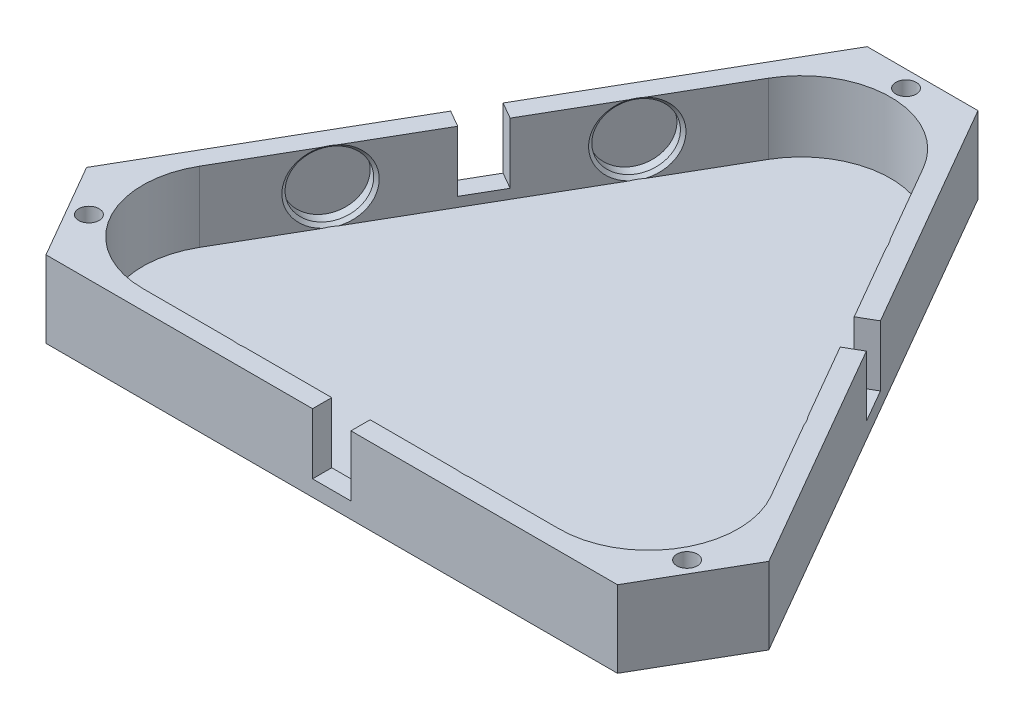
SolidWorks part; units mm, degrees
ref_plane "Plan de face" through (0, 0, 0) normal (0, 0, 1) x (1, 0, 0)
ref_plane "Plan de dessus" through (0, 0, 0) normal (0, 1, 0) x (1, 0, 0)
ref_plane "Plan de droite" through (0, 0, 0) normal (1, 0, 0) x (0, 0, -1)
sketch "Esquisse1" plane through (0, 0, 0) normal (0, 1, 0) x (1, 0, 0)
  line L3 (-62, -35.7957) -> (62, -35.7957)
  line L4 (62, -35.7957) -> (0, 71.5914)
  line L5 (0, 71.5914) -> (-62, -35.7957)
  line L6 (0, 71.5914) -> (0, -35.7957) construction
  line L7 (62, -35.7957) -> (-31, 17.8979) construction
  dimension "D1" = 124
extrude "Boss.-Extru.1" add sketch "Esquisse1" along normal blind 12 separate body
ref_axis "Axe1" through (0, -0.9, 0) along (0, 1, 0)
sketch "Esquisse10" plane through (0, 12, 0) normal (0, 1, 0) x (1, 0, 0)
  circle A0 centre (0, 54) radius 1.6
  circle A1 centre (46.7654, -27) radius 1.6
  circle A2 centre (-46.7654, -27) radius 1.6
  point P9 (0, 0)
  dimension "D1" = 3.2
  dimension "D2" = 54
  dimension "D3" = 3
extrude "Enlèv. mat.-Extru.6" cut sketch "Esquisse10" against normal through all
sketch "Esquisse2" plane through (0, 12, 0) normal (0, 1, 0) x (1, 0, 0)
  line L0 (-8.6603, 56.5914) -> (8.6603, 56.5914)
  line L1 (0, 71.5914) -> (-62, -35.7957) construction
  line L2 (62, -35.7957) -> (0, 71.5914) construction
  line L3 (8.6603, 56.5914) -> (0, 71.5914)
  line L4 (0, 71.5914) -> (-8.6603, 56.5914)
  line L5 (62, -35.7957) -> (53.3397, -20.7957)
  line L6 (53.3397, -20.7957) -> (44.6795, -35.7957)
  line L7 (44.6795, -35.7957) -> (62, -35.7957)
  line L8 (-62, -35.7957) -> (-44.6795, -35.7957)
  line L9 (-44.6795, -35.7957) -> (-53.3397, -20.7957)
  line L10 (-53.3397, -20.7957) -> (-62, -35.7957)
  point P6 (0, 56.5914)
  point P17 (0, 0)
  dimension "D1" = 15
extrude "Enlèv. mat.-Extru.1" cut sketch "Esquisse2" against normal through all
sketch "Esquisse3" plane through (0, 12, 0) normal (0, 1, 0) x (1, 0, 0)
  line L3 (12.1244, 44.5914) -> (-12.1244, 44.5914) construction
  line L4 (44.6795, -11.7957) -> (12.1244, 44.5914)
  line L5 (-12.1244, 44.5914) -> (-44.6795, -11.7957)
  line L10 (-8.6603, 56.5914) -> (8.6603, 56.5914) construction
  line L11 (-32.5551, -32.7957) -> (32.5551, -32.7957)
  line L12 (44.6305, -25.8798) -> (-47.0158, 27.263) construction
  line L13 (0, -40.6074) -> (0, 51.5914) construction
  line L14 (47.0471, 27.0989) -> (-44.6305, -25.8798) construction
  line L15 (-8.6603, 56.5914) -> (-53.3397, -20.7957) construction
  line L16 (53.3397, -20.7957) -> (8.6603, 56.5914) construction
  line L17 (-44.6795, -35.7957) -> (44.6795, -35.7957) construction
  arc A3 (12.1244, 44.5914) -> (-12.1244, 44.5914) centre (0, 37.5914) ccw
  arc A4 (32.5551, -32.7957) -> (44.6795, -11.7957) centre (32.5551, -18.7957) ccw
  arc A5 (-44.6795, -11.7957) -> (-32.5551, -32.7957) centre (-32.5551, -18.7957) ccw
  point P23 (0, 0)
  dimension "D2" = 14
  dimension "D1" = 3
  dimension "D4" = 3
  dimension "D5" = 3
  dimension "D3" = 3
extrude "Enlèv. mat.-Extru.2" cut sketch "Esquisse3" against normal blind 11
sketch "Esquisse4" plane through (0, 12, 0) normal (0, 1, 0) x (1, 0, 0)
  line L0 (29.9019, 13.7998) -> (26.9019, 18.9959)
  line L1 (44.6795, -11.7957) -> (12.1244, 44.5914) construction
  line L2 (26.9019, 18.9959) -> (29.5, 20.4959)
  line L3 (53.3397, -20.7957) -> (8.6603, 56.5914) construction
  line L4 (29.5, 20.4959) -> (32.5, 15.2998)
  line L5 (32.5, 15.2998) -> (29.9019, 13.7998)
  line L14 (-3, -35.7957) -> (-3, -32.7957)
  line L15 (-3, -32.7957) -> (3, -32.7957)
  line L16 (3, -32.7957) -> (3, -35.7957)
  line L17 (3, -35.7957) -> (-3, -35.7957)
  line L18 (-29.5, 20.4959) -> (-26.9019, 18.9959)
  line L19 (-26.9019, 18.9959) -> (-29.9019, 13.7998)
  line L20 (-29.9019, 13.7998) -> (-32.5, 15.2998)
  line L21 (-32.5, 15.2998) -> (-29.5, 20.4959)
  point P8 (28.4019, 16.3979)
  point P9 (31, 17.8979)
  point P10 (31, 17.8979)
  point P21 (0, 0)
  dimension "D1" = 3
  dimension "D2" = 3
extrude "Enlèv. mat.-Extru.3" cut sketch "Esquisse4" against normal blind 9.5
sketch "Esquisse5" plane through (0, 1, 0) normal (0, 1, 0) x (1, 0, 0)
  line L0 (20.0371, 14.6861) -> (22.7371, 10.0096)
  line L2 (21.5051, 8.1436) -> (17.8051, 14.5522)
  line L4 (32.5, 15.2998) -> (29.5, 20.4959) construction
  line L5 (44.6795, -11.7957) -> (12.1244, 44.5914) construction
  line L6 (21.3871, 12.3479) -> (31, 17.8979) construction
  line L7 (20.0371, 14.6861) -> (22.6352, 16.1861)
  line L8 (22.6352, 16.1861) -> (22.1352, 17.0522)
  line L9 (22.1352, 17.0522) -> (17.8051, 14.5522)
  line L11 (25.8352, 10.6436) -> (21.5051, 8.1436)
  line L12 (25.3352, 11.5096) -> (25.8352, 10.6436)
  line L13 (22.7371, 10.0096) -> (25.3352, 11.5096)
  dimension "D1" = 8.1
  dimension "D2" = 1
  dimension "D3" = 2.7
  dimension "D4" = 2
  dimension "D5" = 5
ref_plane "Plan2" through (0, 0, 0) normal (-1, 0, 0) x (0, 0, 1)
ref_plane "Plan3" through (0, 0, 0) normal (-0.5, 0, 0.866) x (0.866, 0, 0.5)
ref_plane "Plan4" through (0, 0, 0) normal (0.5, 0, 0.866) x (0.866, 0, -0.5)
sketch "Esquisse11" plane through (0, 0, 32.7957) normal (0, 0, -1) x (-1, 0, 0)
  line L0 (32.5551, 1) -> (-32.5551, 1) construction
  line L2 (-32.5551, 1) -> (-32.5551, 12) construction
  line L3 (0, 0) -> (0, 20.2129) construction
  circle A0 centre (-17.5551, 6.5) radius 5.075
  circle A1 centre (17.5551, 6.5) radius 5.075
  dimension "D1" = 10.15
  dimension "D3" = 15
  dimension "D2" = 5.5
extrude "Enlèv. mat.-Extru.7" cut sketch "Esquisse11" against normal blind 2
pattern_circular "Répétition circulaire1" count 3 over 360 about axis through (0, -0.9, 0) along (0, 1, 0) of "Enlèv. mat.-Extru.7"
chamfer "Chanfrein1" distance 0.5 angle 45 6 edges at (34.642, 6.5, -5.5897) (22.1619, 6.5, -27.206) (-22.1619, 6.5, -27.206) (-34.642, 6.5, -5.5897) (-12.4801, 6.5, 32.7957) (12.4801, 6.5, 32.7957)
ref_plane "Plan5" through (0, 6.5, 0) normal (0, 1, 0) x (1, 0, 0)
equation "\"D5@Esquisse3\"=\"D1@Esquisse3\""
equation "\"D4@Esquisse3\"=\"D1@Esquisse3\""
